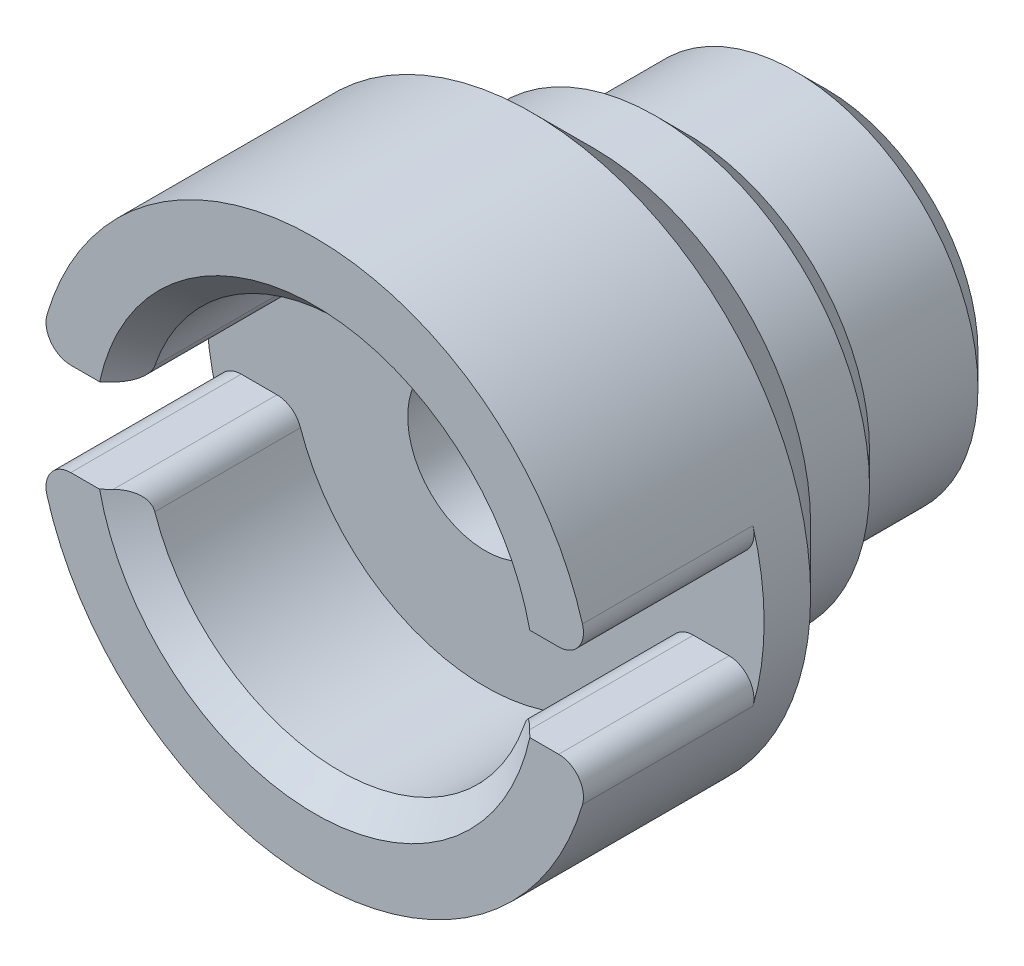
SolidWorks part; units mm, degrees
ref_plane "Front Plane" through (0, 0, 0) normal (0, 0, 1) x (1, 0, 0)
ref_plane "Top Plane" through (0, 0, 0) normal (0, 1, 0) x (1, 0, 0)
ref_plane "Right Plane" through (0, 0, 0) normal (1, 0, 0) x (0, 0, -1)
sketch "Sketch1" plane through (0, 0, 0) normal (0, 0, 1) x (1, 0, 0)
  circle A0 centre (0, 0) radius 2.95
  circle A1 centre (0, 0) radius 1.25
  dimension "D1" = 5.9
  dimension "D2" = 2.5
extrude "Boss-Extrude1" add sketch "Sketch1" along normal blind 3.75
sketch "Sketch2" plane through (0, 0, 3.75) normal (0, 0, 1) x (1, 0, 0)
  circle A0 centre (0, 0) radius 1.25
  circle A1 centre (0, 0) radius 4.5
  circle A2 centre (0, 0) radius 1.25 construction
  dimension "D1" = 9
extrude "Boss-Extrude2" add sketch "Sketch2" along normal blind 4.5
sketch "Sketch3" plane through (0, 0, 8.25) normal (0, 0, 1) x (1, 0, 0)
  circle A0 centre (0, 0) radius 3.15
  dimension "D1" = 6.3
extrude "Cut-Extrude1" cut sketch "Sketch3" against normal blind 2.75
chamfer "Chamfer1" distance 0.4 angle 45 1 edges at (3.15, 0, 8.25)
chamfer "Chamfer2" distance 0.5 angle 45 1 edges at (2.95, 0, 0)
sketch "Sketch4" plane through (0, 0, 3.75) normal (0, 0, -1) x (-1, 0, 0)
  circle A0 centre (0, 0) radius 1.25
  circle A1 centre (0, 0) radius 3.45
  circle A2 centre (0, 0) radius 1.25 construction
  circle A3 centre (0, 0) radius 2.95 construction
  dimension "D1" = 0.5
extrude "Boss-Extrude3" add sketch "Sketch4" along normal blind 1.5
chamfer "Chamfer3" distance 1 angle 45 1 edges at (4.5, 0, 3.75)
chamfer "Chamfer6" distance 0.5 angle 45 1 edges at (-3.45, 0, 2.25)
sketch "Sketch5" plane through (0, 0, 8.25) normal (0, 0, 1) x (1, 0, 0)
  line L1 (6.0839, 0.75) -> (-6.0839, 0.75)
  line L2 (6.0839, 0.75) -> (6.0839, -0.75)
  line L3 (6.0839, -0.75) -> (-6.0839, -0.75)
  line L4 (-6.0839, 0.75) -> (-6.0839, -0.75)
  line L5 (6.0839, 0.75) -> (-6.0839, -0.75) construction
  line L6 (6.0839, -0.75) -> (-6.0839, 0.75) construction
  point P0 (0, 0)
  dimension "D1" = 1.5
extrude "Cut-Extrude2" cut sketch "Sketch5" against normal up to surface (2.75 mm away) up to face at (1.25, 0, 5.5)
fillet "Fillet1" radius 0.4 8 edges at (-3.0594, -0.75, 6.675) (-4.4371, -0.75, 6.875) (-3.0594, 0.75, 6.675) (-4.4371, 0.75, 6.875) (3.0594, -0.75, 6.675) (4.4371, -0.75, 6.875) (3.0594, 0.75, 6.675) (4.4371, 0.75, 6.875)
